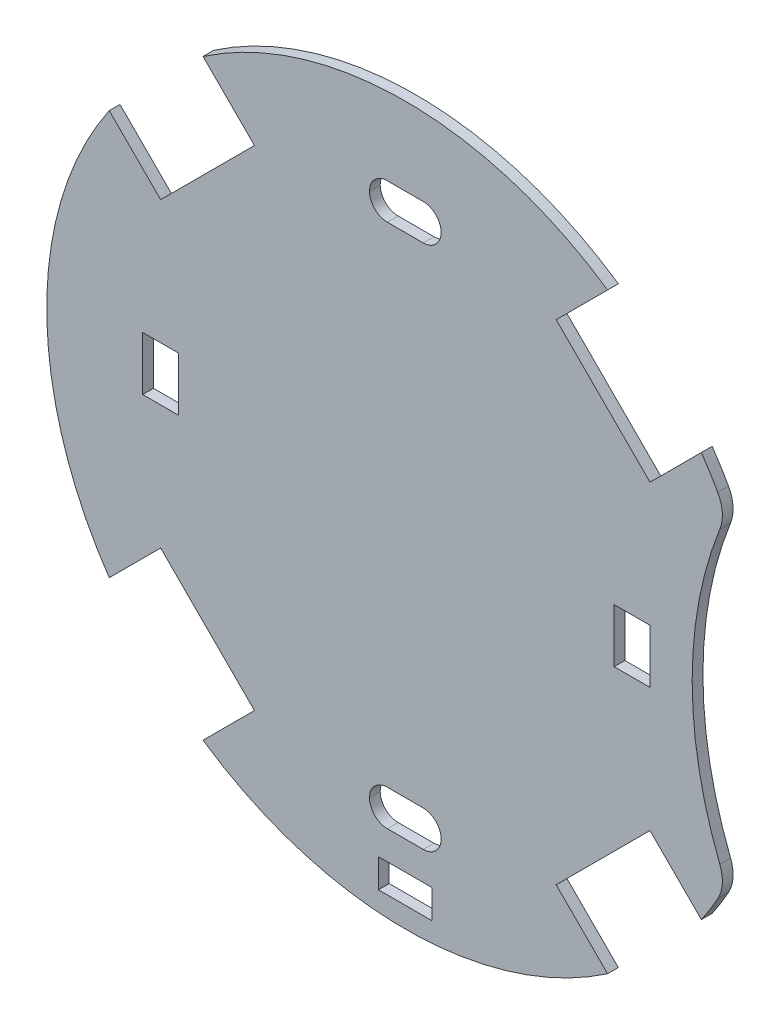
SolidWorks part; units mm, degrees
ref_plane "Alzado" through (0, 0, 0) normal (0, 0, 1) x (1, 0, 0)
ref_plane "Planta" through (0, 0, 0) normal (0, 1, 0) x (1, 0, 0)
ref_plane "Vista lateral" through (0, 0, 0) normal (1, 0, 0) x (0, 0, -1)
sketch "Croquis1" plane through (0, 0, 0) normal (0, 0, 1) x (1, 0, 0)
  circle A0 centre (0, 0) radius 100
  dimension "D1" = 200
extrude "Saliente-Extruir1" add sketch "Croquis1" along normal blind 3
sketch "Croquis3" plane through (0, 0, 3) normal (0, 0, 1) x (1, 0, 0)
  line L0 (0, 0) -> (190, 0) construction
  circle A0 centre (190, 0) radius 110
  dimension "D1" = 220
  dimension "D2" = 190
extrude "Cortar-Extruir1" cut sketch "Croquis3" against normal blind 3
fillet "Redondeo1" radius 10 2 edges at (89.4737, -44.6594, 1.5) (89.4737, 44.6594, 1.5)
sketch "Croquis4" plane through (0, 0, 3) normal (0, 0, 1) x (1, 0, 0)
  line L0 (0, 0) -> (-70.7107, -70.7107) construction
  line L1 (-57.6292, -83.7922) -> (-83.7922, -57.6292)
  line L2 (-57.6292, 83.7922) -> (-42.0729, 68.2358)
  line L3 (-83.7922, -57.6292) -> (-68.2358, -42.0729)
  line L4 (-68.2358, -42.0729) -> (-42.0729, -68.2358)
  line L5 (-42.0729, -68.2358) -> (-57.6292, -83.7922)
  line L6 (-42.0729, 68.2358) -> (-68.2358, 42.0729)
  line L7 (-68.2358, 42.0729) -> (-83.7922, 57.6292)
  line L8 (-83.7922, 57.6292) -> (-57.6292, 83.7922)
  line L9 (83.7922, 57.6292) -> (68.2358, 42.0729)
  line L10 (68.2358, 42.0729) -> (42.0729, 68.2358)
  line L11 (42.0729, 68.2358) -> (57.6292, 83.7922)
  line L12 (57.6292, 83.7922) -> (83.7922, 57.6292)
  line L13 (57.6292, -83.7922) -> (42.0729, -68.2358)
  line L14 (42.0729, -68.2358) -> (68.2358, -42.0729)
  line L15 (68.2358, -42.0729) -> (83.7922, -57.6292)
  line L16 (83.7922, -57.6292) -> (57.6292, -83.7922)
  arc A0 (87.1345, 49.0671) -> (87.1345, -49.0671) centre (0, 0) ccw construction
  point P25 (0, 0)
  dimension "D3" = 18.5
  dimension "D4" = 78
  dimension "D1" = 22
  dimension "D2" = 37
  dimension "D5" = 4
extrude "Cortar-Extruir2" cut sketch "Croquis4" against normal through all
sketch "Croquis6" plane through (0, 0, 3) normal (0, 0, 1) x (1, 0, 0)
  line L0 (-68.2358, 42.0729) -> (-68.2358, -42.0729) construction
  line L1 (-42.0729, 68.2358) -> (42.0729, 68.2358) construction
  line L2 (58.24, 7.5) -> (58.24, -7.5)
  line L3 (-42.0729, -68.2358) -> (42.0729, -68.2358) construction
  line L4 (-63.2358, 0) -> (-73.2358, 0) construction
  line L5 (-63.2358, 0) -> (0, 0) construction
  line L6 (-63.2358, 7.5) -> (-63.2358, -7.5)
  line L7 (-73.2358, 7.5) -> (-73.2358, -7.5)
  line L8 (-68.2358, 42.0729) -> (-42.0729, 68.2358) construction
  line L9 (-42.0729, -68.2358) -> (-68.2358, -42.0729) construction
  line L10 (0, 0) -> (0, -68.24) construction
  line L11 (10, 68.24) -> (10, 78.24)
  line L12 (10, 78.24) -> (-10, 78.24)
  line L13 (10, 68.24) -> (-10, 68.24)
  line L14 (-10, 78.24) -> (-10, 68.24)
  line L15 (68.2358, -42.0729) -> (42.0729, -68.2358) construction
  line L16 (68.24, -7.5) -> (58.24, -7.5)
  line L17 (0, -78.24) -> (0, -86.24) construction
  line L18 (68.24, 7.5) -> (68.24, -7.5)
  line L19 (-10, -68.24) -> (-10, -78.24)
  line L20 (-10, -78.24) -> (10, -78.24)
  line L21 (-10, -68.24) -> (10, -68.24)
  line L22 (10, -78.24) -> (10, -68.24)
  line L23 (0, 0) -> (0, 68.24) construction
  line L24 (58.24, 0) -> (0, 0) construction
  line L25 (68.24, 7.5) -> (58.24, 7.5)
  line L26 (-73.2358, -7.5) -> (-63.2358, -7.5)
  line L27 (-73.2358, 7.5) -> (-63.2358, 7.5)
  line L28 (-7.5, -86.24) -> (7.5, -86.24)
  line L29 (-7.5, -86.24) -> (-10, -78.24) construction
  line L30 (7.5, -86.24) -> (7.5, -94.24)
  line L31 (7.5, -94.24) -> (-7.5, -94.24)
  line L32 (-7.5, -94.24) -> (-7.5, -86.24)
  arc A0 (-56.4086, -82.5716) -> (56.4086, -82.5716) centre (0, 0) ccw construction
  arc A1 (-82.5716, 56.4086) -> (-82.5716, -56.4086) centre (0, 0) ccw construction
  arc A2 (87.7193, 40.4803) -> (87.7193, -40.4803) centre (190, 0) ccw construction
  arc A4 (56.4086, 82.5716) -> (-56.4086, 82.5716) centre (0, 0) ccw construction
  point P44 (0, 0)
  dimension "D2" = 10
  dimension "D3" = 15
  dimension "D4" = 73.2358
  dimension "D5" = 7.5
  dimension "D7" = 10
  dimension "D6" = 68.24
  dimension "D8" = 58.24
  dimension "D9" = 10
  dimension "D10" = 15
  dimension "D11" = 20
  dimension "D12" = 10
  dimension "D13" = 20
  dimension "D14" = 10
  dimension "D15" = 10
  dimension "D16" = 78.24
  dimension "D17" = 7.5
  dimension "D18" = 68.24
  dimension "D19" = 135
  dimension "D20" = 45
  dimension "D21" = 45
extrude "Cortar-Extruir4" cut sketch "Croquis6" against normal blind 10
fillet "Redondeo3" radius 5 8 edges at (10, 68.24, 1.5) (-10, 68.24, 1.5) (10, 78.24, 1.5) (-10, 78.24, 1.5) (10, -78.24, 1.5) (-10, -78.24, 1.5) (10, -68.24, 1.5) (-10, -68.24, 1.5)
